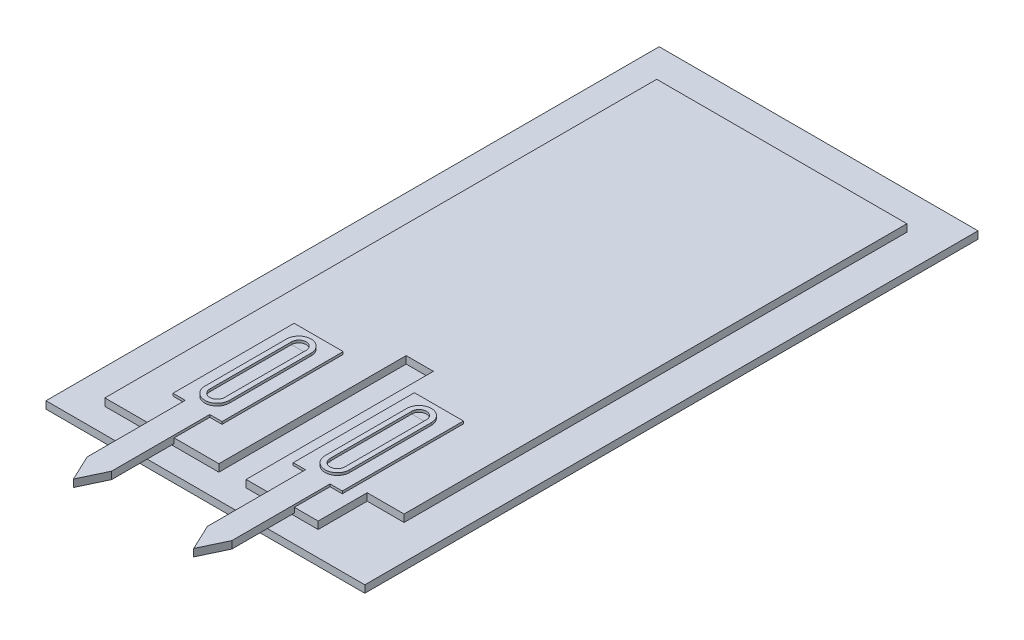
SolidWorks part; units mm, degrees
ref_plane "Front Plane" through (0, 0, 0) normal (0, 0, 1) x (1, 0, 0)
ref_plane "Top Plane" through (0, 0, 0) normal (0, 1, 0) x (1, 0, 0)
ref_plane "Right Plane" through (0, 0, 0) normal (1, 0, 0) x (0, 0, -1)
sketch "Sketch1" plane through (0, 0, 0) normal (0, 1, 0) x (1, 0, 0)
  line L1 (0, 0) -> (13, 0)
  line L2 (0, 0) -> (0, 25)
  line L3 (0, 25) -> (13, 25)
  line L4 (13, 0) -> (13, 25)
  dimension "D1" = 25
  dimension "D2" = 13
extrude "plastic coat" add sketch "Sketch1" along normal blind 0.3
sketch "Sketch2" plane through (0, 0.3, 0) normal (0, 1, 0) x (1, 0, 0)
  line L0 (6.5, 25) -> (6.5, 0) construction
  line L1 (13, 25) -> (0, 25) construction
  line L2 (0, 0) -> (13, 0) construction
  line L3 (0, 12.5) -> (13, 12.5) construction
  line L4 (0, 25) -> (0, 0) construction
  line L5 (13, 0) -> (13, 25) construction
  line L6 (1.4, 1) -> (6.049, 1)
  line L7 (1.4, 23.5) -> (11.6, 23.5)
  line L8 (1.4, 23.5) -> (1.4, 1)
  line L9 (6.049, 1) -> (6.049, 8.636)
  line L10 (11.6, 23.5) -> (11.6, 3)
  line L11 (6.049, 8.636) -> (7.159, 8.636)
  line L12 (7.159, 8.636) -> (7.159, 2.7407)
  line L13 (11.6, 3) -> (10.0964, 3)
  line L14 (10.0964, 3) -> (10.0964, 1)
  line L15 (10.0964, 1) -> (7.159, 1)
  line L16 (7.159, 1) -> (7.159, 2.7407)
  point P13 (6.604, 8.636)
  dimension "D1" = 10.2
  dimension "D2" = 23.5
  dimension "D3" = 8.636
  dimension "D4" = 6.604
  dimension "D5" = 1.11
  dimension "D6" = 2.9374
  dimension "D7" = 2
extrude "aluminum extrude" add sketch "Sketch2" along normal blind 0.3 and the other way blind 0.3 separate body
sketch "Sketch3" plane through (0, 0.6, 0) normal (0, 1, 0) x (1, 0, 0)
  line L0 (6.5, 23.5) -> (6.5, -5.0084) construction
  line L1 (11.6, 23.5) -> (1.4, 23.5) construction
  line L2 (2.7245, 7.3935) -> (2.7245, 2.4524)
  line L3 (3.7245, 1) -> (3.7245, 23.5) construction
  line L4 (2.7245, 2.4524) -> (3.2245, 2.4524)
  line L5 (1.4, 1) -> (6.049, 1) construction
  line L6 (3.2245, 2.4524) -> (3.2245, -1.5476)
  line L7 (0, 0) -> (13, 0) construction
  line L8 (4.2245, -1.5476) -> (4.2245, 2.4524)
  line L9 (4.2245, 2.4524) -> (4.7245, 2.4524)
  line L10 (4.7245, 2.4524) -> (4.7245, 7.3935)
  line L11 (4.7245, 7.3935) -> (2.7245, 7.3935)
  line L12 (3.7245, 7.3935) -> (3.7245, -5.0089) construction
  line L13 (3.2245, -1.5476) -> (3.7245, -2.6065)
  line L14 (3.7245, -2.6065) -> (4.2245, -1.5476)
  line L15 (8.6277, 1) -> (8.6277, 8.9802) construction
  line L16 (7.159, 1) -> (10.0964, 1) construction
  line L17 (7.6277, 7.3935) -> (9.6277, 7.3935)
  line L18 (9.6277, 7.3935) -> (9.6277, 2.4524)
  line L19 (9.6277, 2.4524) -> (9.1277, 2.4524)
  line L20 (9.1277, 2.4524) -> (9.1277, -1.5476)
  line L21 (9.1277, -1.5476) -> (8.6277, -2.6054)
  line L22 (8.6277, -2.6054) -> (8.1277, -1.5476)
  line L23 (8.1277, -1.5476) -> (8.1277, 2.4524)
  line L24 (8.1277, 2.4524) -> (7.6277, 2.4524)
  line L25 (7.6277, 2.4524) -> (7.6277, 7.3935)
  point P32 (0, 0)
  dimension "D1" = 2
  dimension "D2" = 4
  dimension "D3" = 4
  dimension "D4" = 10
  dimension "D5" = 1
  dimension "D6" = 2.4524
  dimension "D7" = 2.4524
  dimension "D8" = 1.171
  dimension "D9" = 2
  dimension "D10" = 4
  dimension "D11" = 1.17
  dimension "D12" = 1
  dimension "D13" = 4
extrude "sensor extrude" add sketch "Sketch3" against normal blind 0.2 and the other way blind 0.1
sketch "Sketch4" plane through (0, 0.7, 0) normal (0, 1, 0) x (1, 0, 0)
  line L0 (3.7245, 7.3935) -> (3.7245, -2.6065) construction
  line L1 (4.7245, 7.3935) -> (2.7245, 7.3935) construction
  line L2 (3.7245, 6.5846) -> (3.7245, 3.2524) construction
  line L3 (4.2245, 6.5846) -> (4.2245, 3.2524)
  line L4 (3.2245, 6.5846) -> (3.2245, 3.2524)
  line L5 (8.6277, 7.3935) -> (8.6277, -2.6054) construction
  line L6 (9.6277, 7.3935) -> (7.6277, 7.3935) construction
  line L7 (8.6277, 6.5846) -> (8.6277, 3.2524) construction
  line L8 (9.1277, 6.5846) -> (9.1277, 3.2524)
  line L9 (8.1277, 6.5846) -> (8.1277, 3.2524)
  line L18 (10.0964, 3) -> (11.6, 3) construction
  line L19 (1.4, 1) -> (6.049, 1) construction
  arc A0 (4.2245, 6.5846) -> (3.2245, 6.5846) centre (3.7245, 6.5846) ccw
  arc A1 (3.2245, 3.2524) -> (4.2245, 3.2524) centre (3.7245, 3.2524) ccw
  arc A2 (9.1277, 6.5846) -> (8.1277, 6.5846) centre (8.6277, 6.5846) ccw
  arc A3 (8.1277, 3.2524) -> (9.1277, 3.2524) centre (8.6277, 3.2524) ccw
  point P7 (3.7245, 4.9185)
  point P19 (8.6277, 4.9185)
  point P24 (8.6277, 2.7524)
  point P27 (8.6277, 7.0846)
  dimension "D2" = 1
  dimension "D6" = 2.2524
  dimension "D1" = 1
  dimension "D3" = 0.2476
  dimension "D4" = 0.8089
  dimension "D5" = 4.0846
extrude "Boss-Extrude6" add sketch "Sketch4" along normal blind 0.1 and the other way blind 0.1
sketch "Sketch8" plane through (0, 0, 0) normal (0, -1, 0) x (1, 0, 0)
  line L0 (3.7245, -1) -> (3.7245, -8.4827) construction
  line L1 (1.4, -1) -> (6.049, -1) construction
  line L2 (8.6277, -1) -> (8.6277, -8.4827) construction
  line L3 (7.159, -1) -> (10.0964, -1) construction
  line L4 (0, 0) -> (13, 0) construction
  line L5 (3.2477, -8.095) -> (2.7477, -8.095)
  line L6 (3.2477, -8.095) -> (3.2477, -7.095)
  line L7 (3.2477, -7.095) -> (2.7477, -7.095)
  line L8 (2.7477, -8.095) -> (2.7477, -7.095)
  line L9 (3.3948, -6.095) -> (2.8948, -6.095)
  line L10 (3.3948, -6.095) -> (3.3948, -5.095)
  line L11 (3.3948, -5.095) -> (2.8948, -5.095)
  line L12 (2.8948, -6.095) -> (2.8948, -5.095)
  line L13 (4.2013, -7.5364) -> (4.7013, -7.5364)
  line L14 (4.2013, -7.5364) -> (4.2013, -6.5364)
  line L15 (4.2013, -6.5364) -> (4.7013, -6.5364)
  line L16 (4.7013, -7.5364) -> (4.7013, -6.5364)
  line L17 (4.5542, -5.5364) -> (4.0542, -5.5364)
  line L18 (4.5542, -5.5364) -> (4.5542, -4.5364)
  line L19 (4.5542, -4.5364) -> (4.0542, -4.5364)
  line L20 (4.0542, -5.5364) -> (4.0542, -4.5364)
  line L21 (0, -25) -> (0, 0) construction
  line L22 (0, -25) -> (0, 0) construction
  line L23 (0, 0) -> (13, 0) construction
  dimension "D1" = 1
  dimension "D2" = 0.5
  dimension "D3" = 4.5364
  dimension "D4" = 1
  dimension "D5" = 1
  dimension "D6" = 2.7477
  dimension "D7" = 2.8948
  dimension "D8" = 5.095
sketch "Sketch10" plane through (0, 0.8, 0) normal (0, 1, 0) x (1, 0, 0)
  line L4 (8.3277, 6.5846) -> (8.3277, 3.2524)
  line L5 (8.9277, 3.2524) -> (8.9277, 6.5846)
  line L6 (8.3277, 6.5846) -> (8.3277, 3.2524)
  line L7 (8.9277, 3.2524) -> (8.9277, 6.5846)
  arc A4 (8.9277, 6.5846) -> (8.3277, 6.5846) centre (8.6277, 6.5846) ccw
  arc A5 (8.3277, 3.2524) -> (8.9277, 3.2524) centre (8.6277, 3.2524) ccw
  arc A6 (8.9277, 6.5846) -> (8.3277, 6.5846) centre (8.6277, 6.5846) ccw
  arc A7 (8.3277, 3.2524) -> (8.9277, 3.2524) centre (8.6277, 3.2524) ccw
  dimension "D1" = 0.2
extrude "Cut-Extrude2" cut sketch "Sketch10" against normal blind 0.1
sketch "Sketch11" plane through (0, 0.8, 0) normal (0, 1, 0) x (1, 0, 0)
  line L4 (3.4245, 6.5846) -> (3.4245, 3.2524)
  line L5 (4.0245, 3.2524) -> (4.0245, 6.5846)
  line L6 (3.4245, 6.5846) -> (3.4245, 3.2524)
  line L7 (4.0245, 3.2524) -> (4.0245, 6.5846)
  arc A4 (4.0245, 6.5846) -> (3.4245, 6.5846) centre (3.7245, 6.5846) ccw
  arc A5 (3.4245, 3.2524) -> (4.0245, 3.2524) centre (3.7245, 3.2524) ccw
  arc A6 (4.0245, 6.5846) -> (3.4245, 6.5846) centre (3.7245, 6.5846) ccw
  arc A7 (3.4245, 3.2524) -> (4.0245, 3.2524) centre (3.7245, 3.2524) ccw
  dimension "D1" = 0.2
extrude "Cut-Extrude3" cut sketch "Sketch11" against normal blind 0.1
